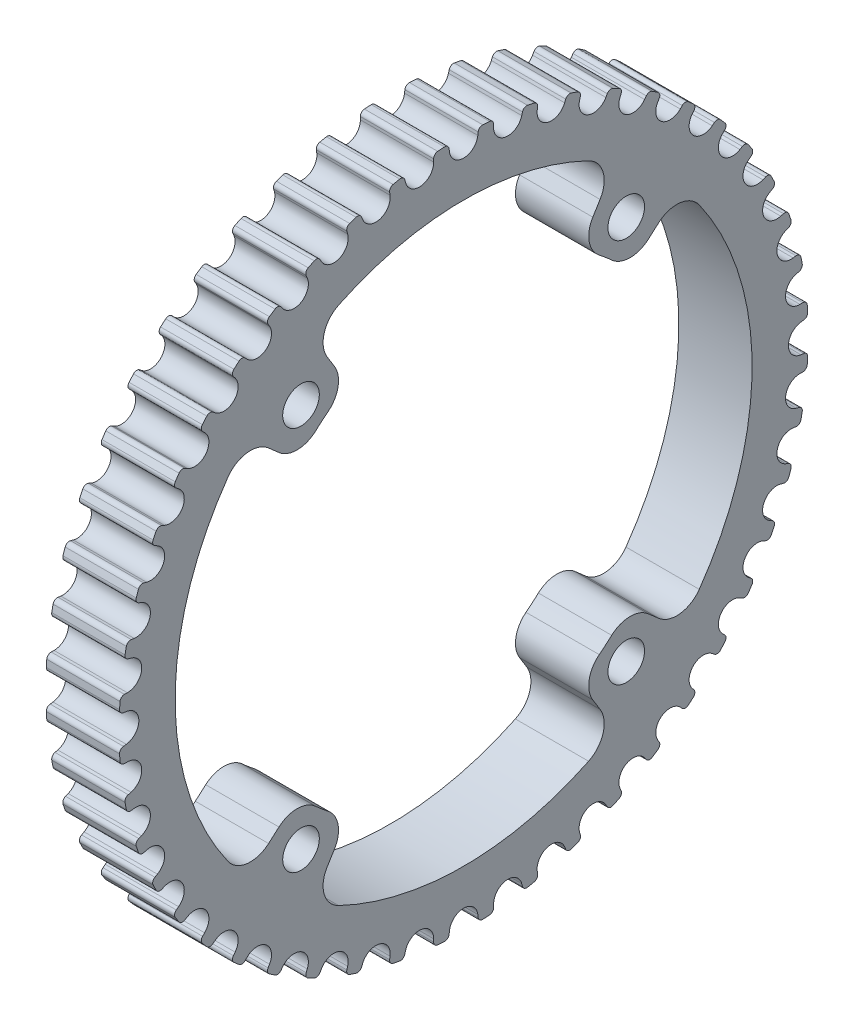
SolidWorks part; units mm, degrees
material "Thornel Mat VMA"
ref_plane "前视基准面" through (0, 0, 0) normal (0, 0, 1) x (1, 0, 0)
ref_plane "上视基准面" through (0, 0, 0) normal (0, 1, 0) x (1, 0, 0)
ref_plane "右视基准面" through (0, 0, 0) normal (1, 0, 0) x (0, 0, -1)
sketch "草图1" plane through (0, 0, 0) normal (0, 0, 1) x (1, 0, 0)
  line L0 (0, 0) -> (64.8368, 0) construction
  line L1 (0, 7.0476) -> (0, 37.623)
  line L2 (0, 37.623) -> (28, 37.623)
  line L3 (28, 37.623) -> (28, 14.0952)
  line L4 (28, 14.0952) -> (20, 14.0952)
  line L5 (20, 14.0952) -> (20, 7.0476)
  line L6 (20, 7.0476) -> (0, 7.0476)
  dimension "L" = 20
  dimension "B" = 28
  dimension "d" = 14.0952
  dimension "d1" = 28.1904
  dimension "da" = 75.246
revolve "旋转1" add sketch "草图1" angle 360 about L0
chamfer "倒角1" distance 1 angle 45 2 edges at (20, 0, 7.0476) (0, 0, 7.0476)
sketch "草图4" plane through (0, 0, 0) normal (-1, 0, 0) x (0, 0, 1)
  line L1 (-2.5, 6.5893) -> (2.5, 6.5893)
  line L2 (-2.5, 6.5893) -> (-2.5, 8.8893)
  line L3 (-2.5, 8.8893) -> (2.5, 8.8893)
  line L4 (2.5, 6.5893) -> (2.5, 8.8893)
  circle A0 centre (0, 0) radius 7.0476 construction
  dimension "键槽宽度" = 5
  dimension "t1" = 2.3
extrude "切除-拉伸1" cut sketch "草图4" against normal through all
ref_axis "基准轴1" through (-0.4, 0, 0) along (1, 0, 0)
sketch "草图6" plane through (0, 0, 0) normal (1, 0, 0) x (0, 0, -1)
  line L0 (0, 0) -> (0, 30.6512) construction
  line L1 (1.5866, 37.1442) -> (1.5484, 36.8329)
  line L2 (2.5688, 37.5352) -> (2.7654, 39.1368)
  line L3 (-2.5688, 37.5352) -> (-2.7654, 39.1368)
  line L4 (-1.5866, 37.1442) -> (-1.5484, 36.8329)
  circle A0 centre (0, 0) radius 37.623 construction
  circle A1 centre (0, 0) radius 35.463 construction
  arc A2 (-1.5484, 36.8329) -> (1.5484, 36.8329) centre (0, 37.023) ccw
  arc A3 (2.7654, 39.1368) -> (-2.7654, 39.1368) centre (0, 0) ccw
  arc A4 (1.5866, 37.1442) -> (2.0897, 37.5649) centre (2.063, 37.0857) cw
  arc A5 (2.0897, 37.5649) -> (2.5688, 37.5352) centre (0, 0) cw
  arc A6 (-2.0897, 37.5649) -> (-2.5688, 37.5352) centre (0, 0) ccw
  arc A7 (-1.5866, 37.1442) -> (-2.0897, 37.5649) centre (-2.063, 37.0857) ccw
  point P7 (0, 3.25)
  point P8 (0, 28.4912)
  point P15 (1.641, 37.5872)
  dimension "D1" = 70.926
  dimension "ra" = 0.48
  dimension "rf" = 1.56
  dimension "hg" = 2.16
  dimension "D3" = 0.48
  dimension "D4" = 1.6136
  dimension "angle" = 14
  dimension "bw" = 3.25
extrude "切除-拉伸2" cut sketch "草图6" along normal up to next
pattern_circular "阵列(圆周)3" count 48 over 360 about axis through (-0.4, 0, 0) along (1, 0, 0) of "切除-拉伸2"
sketch "草图7" plane through (28, 0, 0) normal (1, 0, 0) x (0, 0, -1)
  circle A0 centre (0, 0) radius 40
  dimension "D1" = 80
extrude "切除-拉伸3" cut sketch "草图7" against normal offset from surface (20 mm away) 8 up to face at (0, 4.3451, 0)
sketch "草图15" [suppressed] plane through (8, 0, 0) normal (1, 0, 0) x (0, 0, -1)
  line L0 (0, -31.5) -> (0, 31.5) construction
  line L1 (-31.5, 0) -> (31.5, 0) construction
  line L2 (-31.5, -3) -> (31.5, -3)
  line L3 (3, -31.5) -> (3, 31.5)
  line L4 (-31.5, 3) -> (31.5, 3)
  line L5 (-3, -31.5) -> (-3, 31.5)
  circle A0 centre (0, 0) radius 31.5
  circle A1 centre (0, 0) radius 9
  point P6 (0, 0)
  point P9 (0, 0)
  dimension "D1" = 63
  dimension "D4" = 18
  dimension "D2" = 3
  dimension "D3" = 3
extrude "切除-拉伸9" [suppressed] cut sketch "草图15" against normal blind 10 contours A1 L3 A0 L2 | A1 L4 A0 L3 | A1 L5 A0 L4 | A1 L2 A0 L5
fillet "圆角1" [suppressed] radius 4
sketch "草图16" [suppressed] plane through (8, 0, 0) normal (1, 0, 0) x (0, 0, -1)
  circle A0 centre (0, 0) radius 31.5 construction
  circle A1 centre (31.5, 0) radius 1.55
  circle A2 centre (0, 31.5) radius 1.55
  circle A3 centre (-31.5, 0) radius 1.55
  circle A4 centre (0, -31.5) radius 1.55
  dimension "D1" = 63
  dimension "D2" = 3.1
extrude "切除-拉伸10" [suppressed] cut sketch "草图16" against normal blind 10
sketch "草图17" plane through (8, 0, 0) normal (1, 0, 0) x (0, 0, -1)
  line L0 (17.7553, -21) -> (0, 0) construction
  line L1 (-37.623, 25) -> (37.623, 25) construction
  line L2 (-37.623, 25) -> (-37.623, -25) construction
  line L3 (-37.623, -25) -> (37.623, -25) construction
  line L4 (37.623, 25) -> (37.623, -25) construction
  line L5 (-37.623, 25) -> (37.623, -25) construction
  line L6 (-37.623, -25) -> (37.623, 25) construction
  line L7 (0, 0) -> (49.7141, 0) construction
  line L8 (0, 0) -> (0, 15.7227) construction
  arc A0 (37.5163, -2.8314) -> (37.5649, -2.0897) centre (0, 0) ccw construction
  circle A1 centre (17.7553, -21) radius 2
  circle A2 centre (-17.7553, -21) radius 2
  circle A3 centre (-17.7553, 21) radius 2
  circle A4 centre (17.7553, 21) radius 2
  point P0 (0, 0)
  dimension "D2" = 4
  dimension "D1" = 50
  dimension "D3" = 27.5
  dimension "D4" = 8
sketch "草图18" plane through (8, 0, 0) normal (1, 0, 0) x (0, 0, -1)
  circle A0 centre (0, 0) radius 24
  dimension "D1" = 48
extrude "切除-拉伸11" cut sketch "草图17" against normal blind 10
extrude "切除-拉伸12" cut sketch "草图18" against normal blind 10
sketch "草图19" plane through (8, 0, 0) normal (1, 0, 0) x (0, 0, -1)
  line L0 (0, 0) -> (17.7553, -21) construction
  line L1 (0, 0) -> (16.559, -26.7965)
  line L2 (0, 0) -> (23.67, -20.7842)
  line L3 (14.2673, 0) -> (0, 0) construction
  line L4 (0, 14.024) -> (0, 0) construction
  line L5 (0, 0) -> (16.559, 26.7965)
  line L6 (0, 0) -> (23.67, 20.7842)
  line L7 (0, 0) -> (-16.559, -26.7965)
  line L8 (0, 0) -> (-23.67, -20.7842)
  line L9 (0, 0) -> (-16.559, 26.7965)
  line L10 (0, 0) -> (-23.67, 20.7842)
  circle A0 centre (0, 0) radius 31.5
  circle A1 centre (0, 0) radius 24 construction
  circle A2 centre (0, 0) radius 24
  dimension "D1" = 63
  dimension "D2" = 17
extrude "切除-拉伸13" cut sketch "草图19" against normal blind 10 contours A2 L2 A0 L6 | A2 L7 A0 L1 | A2 L10 A0 L8 | A2 L5 A0 L9 region at (8, -26.515, 0) region at (8, 0, -25.5648) region at (8, 26.515, 0) region at (8, 0, 25.5648)
fillet "圆角2" radius 3 16 edges at (4, 20.7842, 23.67) (4, -20.7842, 23.67) (4, -15.8356, 18.0343) (4, -20.4163, 12.6164) (4, -26.7965, 16.559) (4, -26.7965, -16.559) (4, -20.4163, -12.6164) (4, -15.8356, -18.0343) (4, -20.7842, -23.67) (4, 20.7842, -23.67) (4, 15.8356, -18.0343) (4, 20.4163, -12.6164) (4, 26.7965, -16.559) (4, 26.7965, 16.559) (4, 20.4163, 12.6164) (4, 15.8356, 18.0343)
equation "\"D1@草图6\" = \"da@草图1\"  - \"hg@草图6\" - \"hg@草图6\""
equation "\"D3@草图6\" = \"ra@草图6\""
